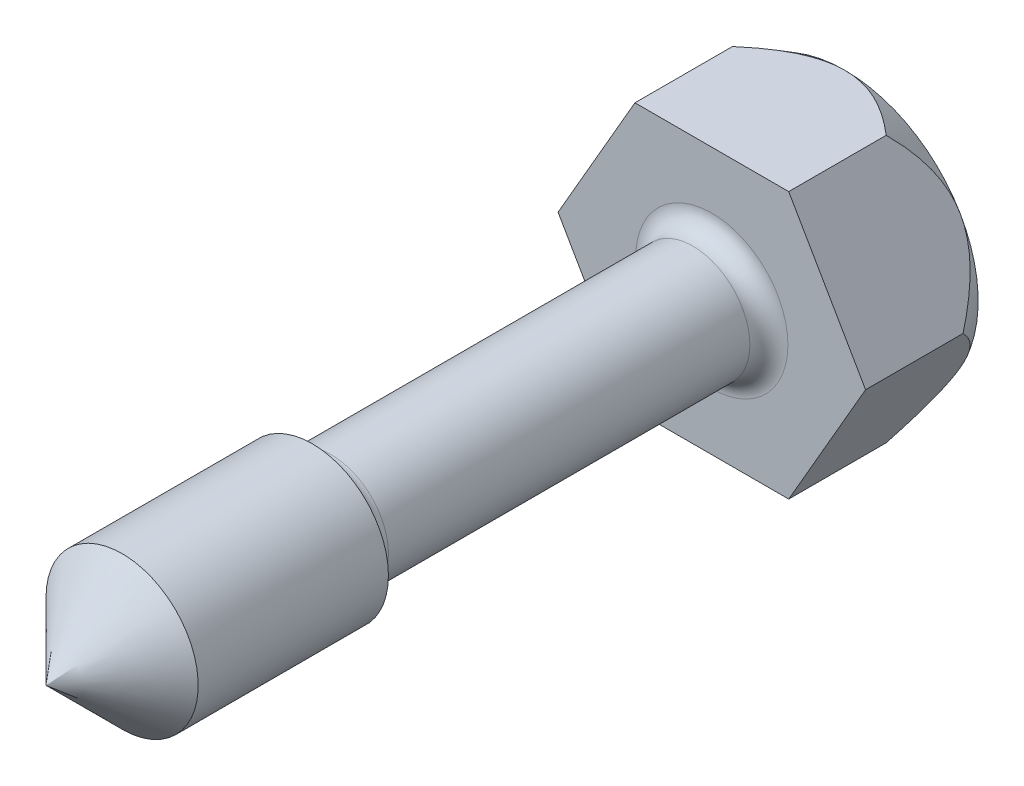
SolidWorks part; units mm, degrees
ref_plane "Front Plane" through (0, 0, 0) normal (0, 0, 1) x (1, 0, 0)
ref_plane "Top Plane" through (0, 0, 0) normal (0, 1, 0) x (1, 0, 0)
ref_plane "Right Plane" through (0, 0, 0) normal (1, 0, 0) x (0, 0, -1)
sketch "Sketch1" plane through (0, 0, 0) normal (0, 0, 1) x (1, 0, 0)
  line L1 (4.0415, 7) -> (-4.0415, 7)
  line L2 (-4.0415, 7) -> (-8.0829, 0)
  line L3 (-8.0829, 0) -> (-4.0415, -7)
  line L4 (-4.0415, -7) -> (4.0415, -7)
  line L5 (4.0415, -7) -> (8.0829, 0)
  line L6 (8.0829, 0) -> (4.0415, 7)
  circle A0 centre (0, 0) radius 7 construction
  dimension "D1" = 14
extrude "Boss-Extrude1" add sketch "Sketch1" along normal blind 7
sketch "Sketch2" plane through (0, 0, 0) normal (0, 1, 0) x (1, 0, 0)
  line L0 (0, 34.92) -> (0, -49.3036) construction
  line L1 (-4, -7) -> (-4, -42)
  line L2 (4.0415, -7) -> (-4.0415, -7) construction
  line L3 (-4, -42) -> (0, -42)
  line L4 (0, -42) -> (0, -7)
  line L5 (0, -7) -> (-4, -7)
  dimension "D1" = 8
  dimension "D2" = 35
revolve "Revolve1" add sketch "Sketch2" angle 360 about L0
cosmetic thread "Cosmetic Thread1" parameters "D2"=6.619
sketch "Sketch3" plane through (0, 0, 0) normal (0, 1, 0) x (1, 0, 0)
  line L0 (0, 11.1629) -> (0, -53.9582) construction
  line L1 (-4, -28) -> (-3, -28)
  line L2 (-4, -7) -> (-4, -42) construction
  line L3 (-3, -28) -> (-3, -7)
  line L4 (4.0415, -7) -> (-4.0415, -7) construction
  line L5 (-3, -7) -> (-4, -7)
  line L6 (-4, -7) -> (4, -7) construction
  line L7 (-4, -7) -> (-4, -28)
  line L8 (-4, -42) -> (4, -42) construction
  dimension "D1" = 6
  dimension "D2" = 14
revolve "Cut-Revolve1" cut sketch "Sketch3" angle 360 about L0
sketch "Sketch5" plane through (0, 0, 0) normal (0, 1, 0) x (1, 0, 0)
  line L0 (0, 15.8234) -> (0, -45.6931) construction
  line L1 (0, -42) -> (-4, -38.0001)
  line L2 (-4, -28) -> (-4, -42) construction
  line L3 (-4, -38.0001) -> (-4, -42)
  line L4 (-4, -42) -> (4, -42) construction
  line L5 (-4, -42) -> (0, -42)
  dimension "D1" = 45
  dimension "D2" = 0.0001
revolve "Cut-Revolve11" cut sketch "Sketch5" angle 360 about L0
fillet "Fillet1" radius 1 2 edges at (-3, 0, 28) (-3, 0, 7)
sketch "Sketch6" plane through (0, 0, 0) normal (0, 0, -1) x (-1, 0, 0)
  line L0 (-4.0415, 7) -> (4.0415, 7) construction
  circle A0 centre (0, 0) radius 7
extrude "Cut-Extrude1" cut sketch "Sketch6" against normal through all draft 30 flip side to cut
